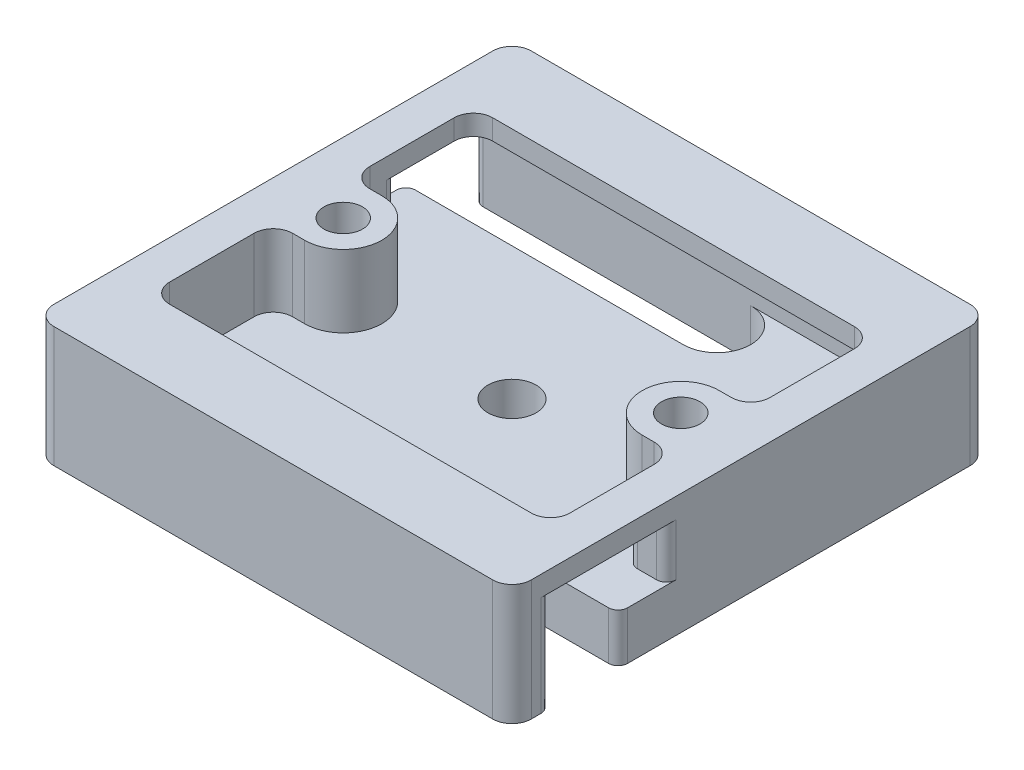
SolidWorks part; units mm, degrees
ref_plane "Alzado" through (0, 0, 0) normal (0, 0, 1) x (1, 0, 0)
ref_plane "Planta" through (0, 0, 0) normal (0, 1, 0) x (1, 0, 0)
ref_plane "Vista lateral" through (0, 0, 0) normal (1, 0, 0) x (0, 0, -1)
sketch "Croquis1" plane through (0, 0, 0) normal (0, 1, 0) x (1, 0, 0)
  line L0 (24.75, -17.25) -> (-4, -17.25) construction
  line L1 (-18.5, -18.5) -> (18.5, -18.5) construction
  line L2 (-18.5, -18.5) -> (-18.5, 18.5) construction
  line L3 (-18.5, 18.5) -> (18.5, 18.5) construction
  line L4 (18.5, -18.5) -> (18.5, 18.5) construction
  line L5 (-18.5, -18.5) -> (18.5, 18.5) construction
  line L6 (-18.5, 18.5) -> (18.5, -18.5) construction
  line L7 (-20.75, -20.75) -> (20.75, -20.75) construction
  line L8 (-20.75, -20.75) -> (-20.75, 20.75) construction
  line L9 (-20.75, 20.75) -> (20.75, 20.75) construction
  line L10 (20.75, -20.75) -> (20.75, 20.75) construction
  line L11 (-20.75, -20.75) -> (20.75, 20.75) construction
  line L12 (-20.75, 20.75) -> (20.75, -20.75) construction
  line L13 (-24.75, -24.75) -> (24.75, -24.75)
  line L14 (-24.75, -24.75) -> (-24.75, 24.75)
  line L15 (-24.75, 24.75) -> (24.75, 24.75)
  line L16 (24.75, -24.75) -> (24.75, 24.75)
  line L17 (-24.75, -24.75) -> (24.75, 24.75) construction
  line L18 (-24.75, 24.75) -> (24.75, -24.75) construction
  line L19 (24.75, -20.75) -> (-4, -20.75)
  line L20 (24.75, -13.75) -> (-4, -13.75)
  line L21 (-7.5, 0) -> (-7.5, -17.25) construction
  line L22 (-24.75, 17.25) -> (4, 17.25) construction
  line L23 (-24.75, 20.75) -> (4, 20.75)
  line L24 (-24.75, 13.75) -> (4, 13.75)
  line L25 (7.5, 17.25) -> (7.5, 0) construction
  line L26 (-4, -20.75) -> (-20.75, -20.75)
  line L27 (-20.75, -20.75) -> (-20.75, 8.75)
  line L28 (4, 20.75) -> (20.75, 20.75)
  line L29 (20.75, 20.75) -> (20.75, -8.75)
  line L30 (-20.75, 8.75) -> (-24.75, 8.75)
  line L31 (20.75, -8.75) -> (24.75, -8.75)
  circle A0 centre (0, 0) radius 7.5 construction
  arc A1 (24.75, -20.75) -> (24.75, -13.75) centre (24.75, -17.25) ccw
  arc A2 (-4, -13.75) -> (-4, -20.75) centre (-4, -17.25) ccw
  arc A3 (-24.75, 20.75) -> (-24.75, 13.75) centre (-24.75, 17.25) ccw
  arc A4 (4, 13.75) -> (4, 20.75) centre (4, 17.25) ccw
  circle A5 centre (0, 0) radius 2.5
  point P0 (0, 0)
  point P5 (0, 0)
  point P19 (10.375, -17.25)
  point P28 (-10.375, 17.25)
  dimension "D7" = 3.5
  dimension "D8" = 15
  dimension "D12" = 5
  dimension "D1" = 37
  dimension "D2" = 37
  dimension "D3" = 2.25
  dimension "D4" = 2.25
  dimension "D10" = 5
  dimension "D11" = 5
  dimension "D5" = 4
  dimension "D6" = 49.5
  dimension "D9" = 4
extrude "Saliente-Extruir1" add sketch "Croquis1" against normal blind 5 contours L27 L30 L14 L13 L16 L19 L26 | A4 L24 L14 L30 L27 L26 A2 L20 L16 L31 L29 L28 A0 | L29 L31 L16 L15 L14 L23 L28 region at (-24.1523, 0, 8) region at (-24.1041, 0, -11.25) region at (-24.1523, 0, -22.75)
extrude "Saliente-Extruir2" add sketch "Croquis1<3>" along normal blind 5.5 contours L27 L30 L14 L13 L16 L19 L26 | L29 L31 L16 L15 L14 L23 L28 region at (-24.1523, 0, 8) region at (-24.1523, 0, -22.75)
sketch "Croquis1<3>" plane through (0, 0, 0) normal (0, 1, 0) x (1, 0, 0) same geometry as "Croquis1"
sketch "Croquis2" plane through (0, 5.5, 0) normal (0, 1, 0) x (1, 0, 0)
  line L12 (-24.75, 24.75) -> (24.75, 24.75)
  line L33 (24.75, 24.75) -> (24.75, -24.75)
  line L34 (24.75, -24.75) -> (-24.75, -24.75)
  line L35 (-24.75, -24.75) -> (-24.75, 24.75)
  line L37 (-20.75, -20.75) -> (-20.75, 8.75) construction
  line L38 (-20.75, -24.75) -> (-20.75, 24.75)
  line L40 (20.75, 24.75) -> (20.75, -24.75)
  line L41 (20.75, 20.75) -> (20.75, -8.75) construction
  line L42 (-20.75, 16.75) -> (20.75, 16.75)
  line L43 (20.75, -16.75) -> (-20.75, -16.75)
  line L44 (24.75, -20.75) -> (-20.75, -20.75) construction
  line L45 (-24.75, 20.75) -> (20.75, 20.75) construction
  line M9 (-20.75, -20.75) -> (-20.75, 8.75)
  line M10 (-20.75, 8.75) -> (-24.75, 8.75)
  line M11 (-24.75, 8.75) -> (-24.75, -24.75)
  line M12 (-24.75, -24.75) -> (24.75, -24.75)
  line M13 (24.75, -24.75) -> (24.75, -20.75)
  line M14 (24.75, -20.75) -> (-20.75, -20.75)
  dimension "D1" = 4
  dimension "D2" = 4
extrude "Saliente-Extruir5" add sketch "Croquis2" along normal blind 2 and the other way blind 0.1 contours L38 L42 L40 L12 | L38 L12 L35 M10 | L40 L43 M9 M14 | L40 L38 L34 M14 | L38 M12 M9 M10 M11 | L12 L40 L33 M14 | L40 M14 M12 M13 region at (-22.75, 5.5, -16.75) region at (0, 5.5, -20.75) region at (-22.75, 5.5, 8) region at (22.75, 5.5, -2) region at (0, 5.5, 22.75) region at (0, 5.5, 18.75) region at (22.75, 5.5, 22.75)
sketch "Croquis3" plane through (0, 7.5, 0) normal (0, 1, 0) x (1, 0, 0)
  line L0 (-24.75, -24.75) -> (-24.75, 24.75) construction
  line L1 (-24.75, -4) -> (-17.5, -4)
  line L2 (-24.75, -4) -> (-24.75, 4)
  line L3 (-24.75, 4) -> (-17.5, 4)
  line L4 (-17.5, -4) -> (-17.5, 4)
  line L5 (0, 24.75) -> (0, -24.75) construction
  line L6 (-24.75, 24.75) -> (24.75, 24.75) construction
  line L7 (-24.75, -24.75) -> (24.75, -24.75) construction
  line L8 (-24.75, 0) -> (20.75, 0) construction
  line L9 (20.75, 20.75) -> (20.75, -8.75) construction
  arc A0 (-17.5, 4) -> (-17.5, -4) centre (-17.5, 0) cw
  circle A1 centre (-17.5, 0) radius 2
  point P19 (-13.5, 0)
  line M7 (-20.75, -16.75) -> (-20.75, 16.75)
  line M10 (-24.75, 24.75) -> (-24.75, -24.75)
  dimension "D3" = 4
  dimension "D2" = 4
  dimension "D1" = 17.5
extrude "Saliente-Extruir6" add sketch "Croquis3" against normal up to surface (7.5 mm away) contours L3 L1 M10 M7 | A1 L4 L3 L1 M7 | A1 L4 A0 region at (-22.75, 7.5, 0) region at (-20.6637, 7.5, 0) region at (-17.4106, 7.5, 3) up to face at (0, 0, 2.5)
extrude "Cortar-Extruir1" cut sketch "Croquis3<3>" against normal up to next contours A1
sketch "Croquis3<3>" plane through (0, 7.5, 0) normal (0, 1, 0) x (1, 0, 0) same geometry as "Croquis3"
mirror "Simetría1" about plane through (0, 0, 0) normal (1, 0, 0) of "Saliente-Extruir6", "Cortar-Extruir1"
sketch "Croquis4" plane through (0, -5, 0) normal (0, -1, 0) x (1, 0, 0)
  circle A0 centre (17.5, 0) radius 2 construction
  circle A1 centre (-17.5, 0) radius 2 construction
  circle A2 centre (17.5, 0) radius 2
  circle A3 centre (-17.5, 0) radius 2
  circle A4 centre (-17.5, 0) radius 3.5
  circle A5 centre (17.5, 0) radius 3.5
  dimension "D1" = 1.5
  dimension "D2" = 1.5
  dimension "D4" = 7
  dimension "D5" = 4
  dimension "D3" = 35
extrude "Cortar-Extruir2" cut sketch "Croquis4" against normal blind 3
fillet "Redondeo1" radius 2 8 edges at (-20.75, 3.75, -4) (-20.75, 3.75, 4) (20.75, 3.75, 4) (20.75, 3.75, -4) (20.75, 6.45, -16.75) (-20.75, 6.45, 16.75) (-20.75, 6.45, -16.75) (20.75, 6.45, 16.75)
fillet "Redondeo2" radius 2 6 edges at (-24.75, 1.25, -24.75) (24.75, 1.25, -24.75) (-24.75, 1.25, 24.75) (24.75, 1.25, 24.75) (20.75, 2.7, -20.75) (-20.75, 2.7, 20.75)
fillet "Redondeo3" radius 1 8 edges at (20.75, 2.7, 8.75) (24.75, 2.7, 8.75) (24.75, -2.5, 13.75) (-24.75, -2.5, -13.75) (-24.75, 2.7, -8.75) (-20.75, 2.7, -8.75) (24.75, 0.2, 20.75) (-24.75, 0.2, -20.75)
equation "\"D2@Croquis1\"=\"D1@Croquis1\""
equation "\"D9@Croquis1\"=\"D5@Croquis1\""
